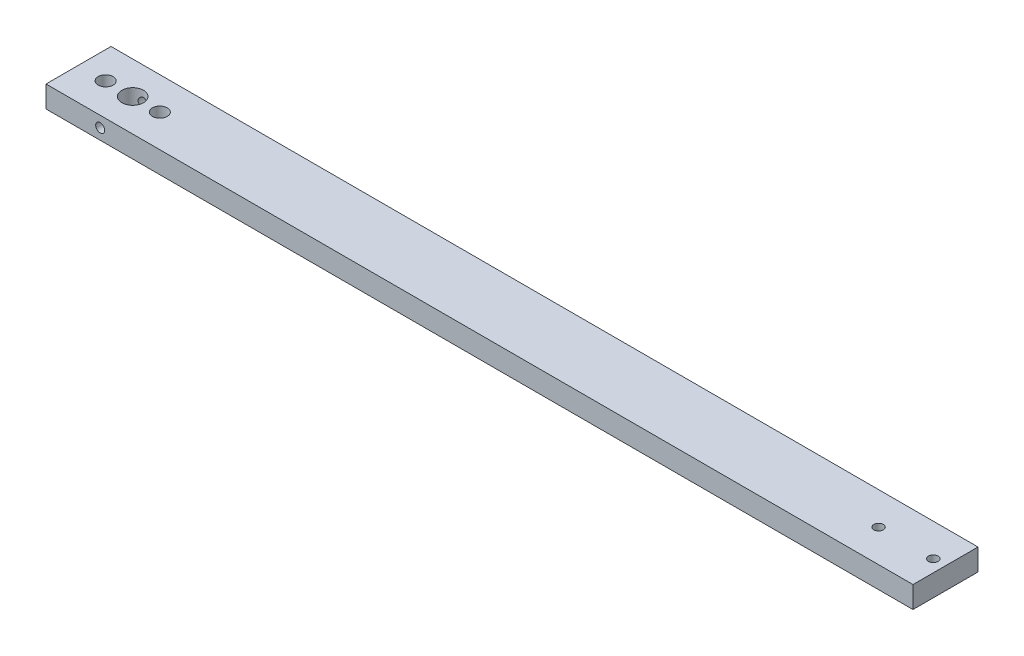
SolidWorks part; units mm, degrees
material "6061 Alloy"
ref_plane "Front Plane" through (0, 0, 0) normal (0, 0, 1) x (1, 0, 0)
ref_plane "Top Plane" through (0, 0, 0) normal (0, 1, 0) x (1, 0, 0)
ref_plane "Right Plane" through (0, 0, 0) normal (1, 0, 0) x (0, 0, -1)
sketch "Sketch1" plane through (0, 0, 0) normal (0, 1, 0) x (1, 0, 0)
  line L0 (-20, 12) -> (300, 12)
  line L1 (-20, -12) -> (300, -12)
  line L3 (300, 12) -> (300, -12)
  line L7 (-20, 12) -> (-20, -12)
  line L10 (0, 5) -> (0, -5) construction
  circle A0 centre (-10, 0) radius 2.75
  circle A1 centre (10, 0) radius 2.75
  circle A2 centre (295.5, 0) radius 1.75
  circle A3 centre (275.3, 0) radius 1.75
  circle A4 centre (0, 0) radius 4
  point P1 (-20, 0)
  dimension "D1" = 20
  dimension "D3" = 10
  dimension "D4" = 3.5
  dimension "D6" = 5.5
  dimension "D7" = 4.5
  dimension "D10" = 8
  dimension "D2" = 10
  dimension "D5" = 24
  dimension "D8" = 300
  dimension "D9" = 20.2
extrude "Boss-Extrude1" add sketch "Sketch1" along normal blind 4 and the other way blind 4
hole_wizard "Tap Drill for M4x0.7 Tap1" positions "Sketch2" profile "Sketch3" hole size "M4x0.7" standard "ANSI Metric" end condition up to next
sketch "Sketch2" plane through (0, 0, 12) normal (0, 0, 1) x (1, 0, 0)
  point P0 (0, 0)
sketch "Sketch3" plane through (0, 0, 12) normal (1, 0, 0) x (0, -1, 0)
  line L0 (0, 0) -> (0, 8)
  line L1 (0, 8) -> (1.65, 8)
  line L2 (1.65, 8) -> (1.65, 0)
  line L5 (1.65, 0) -> (0, 0)
  line L11 (0, -6.35) -> (0, 107.95) construction
  dimension "Thru Hole Dia." = 3.3
  dimension "Thru Hole Depth" = 8
hole_wizard "Tap Drill for M4x0.7 Tap2" positions "Sketch4" profile "Sketch5" hole size "M4x0.7" standard "ANSI Metric" end condition up to next
sketch "Sketch4" plane through (0, 0, -12) normal (0, 0, -1) x (-1, 0, 0)
  point P0 (0, 0)
sketch "Sketch5" plane through (0, 0, -12) normal (1, 0, 0) x (0, 1, 0)
  line L0 (0, 0) -> (0, 8)
  line L1 (0, 8) -> (1.65, 8)
  line L2 (1.65, 8) -> (1.65, 0)
  line L5 (1.65, 0) -> (0, 0)
  line L11 (0, -6.35) -> (0, 107.95) construction
  dimension "Thru Hole Dia." = 3.3
  dimension "Thru Hole Depth" = 8
